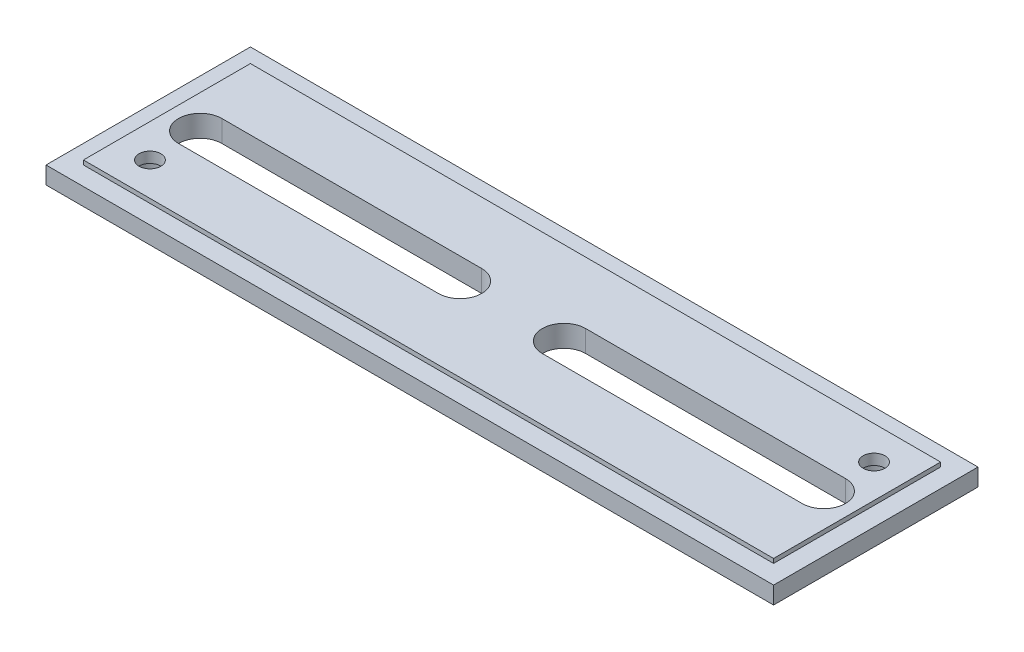
SolidWorks part; units mm, degrees
ref_plane "Front Plane" through (0, 0, 0) normal (0, 0, 1) x (1, 0, 0)
ref_plane "Top Plane" through (0, 0, 0) normal (0, 1, 0) x (1, 0, 0)
ref_plane "Right Plane" through (0, 0, 0) normal (1, 0, 0) x (0, 0, -1)
sketch "Sketch1" plane through (0, 0, 0) normal (0, 1, 0) x (1, 0, 0)
  line L1 (-66.675, -18.7325) -> (66.675, -18.7325)
  line L2 (-66.675, -18.7325) -> (-66.675, 18.7325)
  line L3 (-66.675, 18.7325) -> (66.675, 18.7325)
  line L4 (66.675, -18.7325) -> (66.675, 18.7325)
  line L5 (-66.675, -18.7325) -> (66.675, 18.7325) construction
  line L6 (-66.675, 18.7325) -> (66.675, -18.7325) construction
  point P0 (0, 0)
  dimension "D1" = 133.35
  dimension "D2" = 37.465
extrude "Boss-Extrude1" add sketch "Sketch1" along normal blind 3.175
sketch "Sketch2" plane through (0, 3.175, 0) normal (0, 1, 0) x (1, 0, 0)
  line L0 (63.246, 0) -> (66.675, 0) construction
  line L1 (-63.246, -15.3035) -> (63.246, -15.3035)
  line L2 (-63.246, -15.3035) -> (-63.246, 15.3035)
  line L3 (-63.246, 15.3035) -> (63.246, 15.3035)
  line L4 (63.246, -15.3035) -> (63.246, 15.3035)
  line L5 (-63.246, -15.3035) -> (63.246, 15.3035) construction
  line L6 (-63.246, 15.3035) -> (63.246, -15.3035) construction
  line L7 (66.675, -18.7325) -> (66.675, 18.7325) construction
  line L8 (0, 15.3035) -> (0, 18.7325) construction
  line L9 (66.675, 18.7325) -> (-66.675, 18.7325) construction
  point P0 (0, 0)
  dimension "D1" = 3.429
extrude "Boss-Extrude2" add sketch "Sketch2" along normal blind 0.7937
sketch "Sketch3" plane through (0, 0, 0) normal (0, 1, 0) x (1, 0, 0)
  line L0 (-9.525, 0) -> (-57.15, 0) construction
  line L1 (-9.525, -3.9688) -> (-57.15, -3.9688)
  line L2 (-9.525, 3.9688) -> (-57.15, 3.9687)
  arc A0 (-9.525, -3.9688) -> (-9.525, 3.9688) centre (-9.525, 0) ccw
  arc A1 (-57.15, 3.9687) -> (-57.15, -3.9688) centre (-57.15, 0) ccw
  point P3 (-33.3375, 0)
  dimension "D1" = 9.525
  dimension "D2" = 57.15
  dimension "D3" = 7.9375
extrude "Cut-Extrude1" cut sketch "Sketch3" along normal up to next
mirror "Mirror1" about plane through (0, 0, 0) normal (1, 0, 0) of "Cut-Extrude1"
sketch "Sketch5" plane through (0, 0, 0) normal (0, 1, 0) x (1, 0, 0)
  line L0 (57.15, 9.2075) -> (-57.15, -9.2075) construction
  line L1 (-66.675, -18.7325) -> (66.675, -18.7325) construction
  line L2 (-66.675, 18.7325) -> (-66.675, -18.7325) construction
  circle A0 centre (-57.15, -9.2075) radius 2
  circle A1 centre (57.15, 9.2075) radius 2
  point P4 (0, 0)
  dimension "D1" = 4
  dimension "D2" = 9.525
  dimension "D3" = 9.525
extrude "Cut-Extrude2" cut sketch "Sketch5" along normal up to next
sketch "Sketch6" plane through (0, 0, 0) normal (0, -1, 0) x (-1, 0, 0)
  circle A0 centre (57.15, -9.2075) radius 3.175
  circle A1 centre (-57.15, 9.2075) radius 3.175
  dimension "D1" = 6.35
extrude "Cut-Extrude3" cut sketch "Sketch6" against normal blind 2
